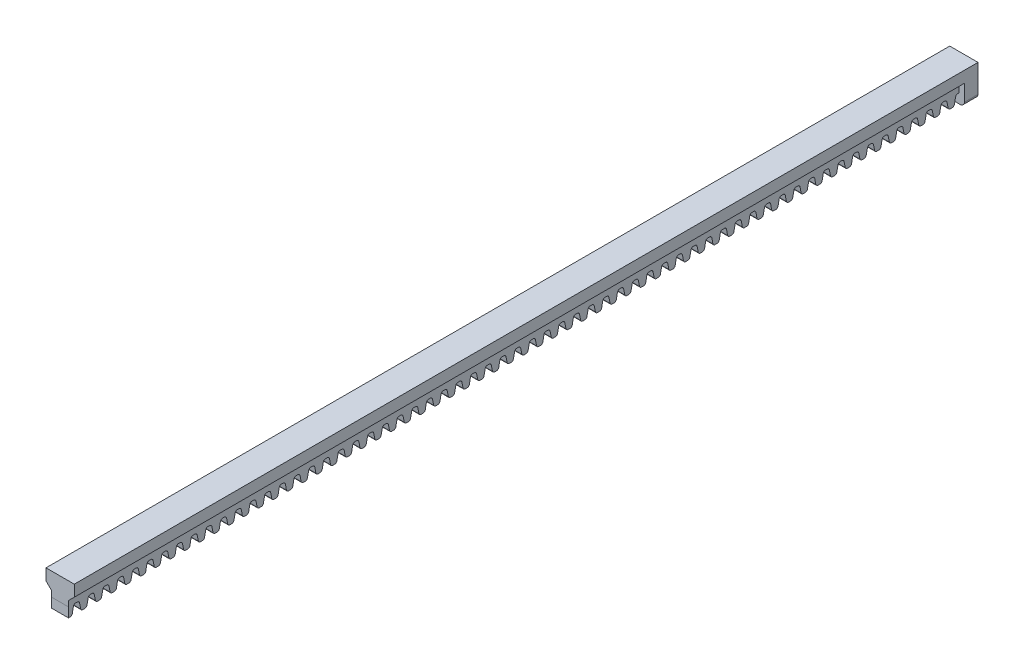
SolidWorks part; units mm, degrees
ref_plane "Ön Düzlem" through (0, 0, 0) normal (0, 0, 1) x (1, 0, 0)
ref_plane "Üst Düzlem" through (0, 0, 0) normal (0, 1, 0) x (1, 0, 0)
ref_plane "Sağ Düzlem" through (0, 0, 0) normal (1, 0, 0) x (0, 0, -1)
sketch "Sketch1" plane through (0, 0, 0) normal (0, 0, 1) x (1, 0, 0)
  line L0 (3.175, 2.54) -> (-3.175, 2.54)
  line L1 (3.175, 2.54) -> (3.175, 0)
  line L2 (-3.175, 0) -> (-1.905, -1.27)
  line L3 (-3.175, 0) -> (-3.175, 2.54)
  line L4 (1.905, -1.27) -> (3.175, 0)
  line L5 (1.905, -1.27) -> (1.905, -2.54)
  line L6 (-1.905, -1.27) -> (-1.905, -2.54)
  line L7 (-1.905, -2.54) -> (1.905, -2.54)
extrude "Boss-Extrude1" add sketch "Sketch1" along normal blind 200
sketch "Sketch2" plane through (1.905, 0, 0) normal (1, 0, 0) x (0, 0, -1)
  line L0 (-4.0649, -2.9484) -> (-4.3253, -4.2507)
  line L1 (-4.7367, -4.6515) -> (-5.2405, -4.659)
  line L2 (-5.7387, -4.2506) -> (-5.9991, -2.9484)
  line L3 (-6.4973, -2.54) -> (-3.5667, -2.54)
  line L4 (-109.7289, -2.9484) -> (-109.9893, -4.2506)
  line L5 (-6.8687, -2.54) -> (-9.7993, -2.54)
  line L6 (-7.6273, -4.2506) -> (-7.3669, -2.9484)
  line L7 (-8.6293, -4.6515) -> (-8.1255, -4.659)
  line L8 (-9.3011, -2.9484) -> (-9.0407, -4.2506)
  line L9 (-10.6689, -2.9484) -> (-10.9293, -4.2506)
  line L10 (-11.3407, -4.6515) -> (-11.8445, -4.659)
  line L11 (-12.3427, -4.2506) -> (-12.6031, -2.9484)
  line L12 (-13.1013, -2.54) -> (-10.1707, -2.54)
  line L13 (-13.4727, -2.54) -> (-16.4033, -2.54)
  line L14 (-14.2313, -4.2506) -> (-13.9709, -2.9484)
  line L15 (-15.2333, -4.6515) -> (-14.7295, -4.659)
  line L16 (-15.9051, -2.9484) -> (-15.6447, -4.2506)
  line L17 (-17.2729, -2.9484) -> (-17.5334, -4.2506)
  line L18 (-17.9447, -4.6515) -> (-18.4486, -4.659)
  line L19 (-18.9467, -4.2506) -> (-19.2072, -2.9484)
  line L20 (-19.7053, -2.54) -> (-16.7748, -2.54)
  line L21 (-20.0768, -2.54) -> (-23.0073, -2.54)
  line L22 (-20.8353, -4.2506) -> (-20.5749, -2.9484)
  line L23 (-21.8373, -4.6515) -> (-21.3335, -4.659)
  line L24 (-22.5092, -2.9484) -> (-22.2487, -4.2506)
  line L25 (-23.8769, -2.9484) -> (-24.1373, -4.2506)
  line L26 (-24.5487, -4.6515) -> (-25.0526, -4.659)
  line L27 (-25.5507, -4.2506) -> (-25.8111, -2.9484)
  line L28 (-26.3093, -2.54) -> (-23.3788, -2.54)
  line L29 (-26.6807, -2.54) -> (-29.6113, -2.54)
  line L30 (-27.4393, -4.2506) -> (-27.1789, -2.9484)
  line L31 (-28.4413, -4.6515) -> (-27.9375, -4.659)
  line L32 (-29.1131, -2.9484) -> (-28.8527, -4.2506)
  line L33 (-30.4809, -2.9484) -> (-30.7413, -4.2506)
  line L34 (-31.1527, -4.6515) -> (-31.6565, -4.659)
  line L35 (-32.1547, -4.2506) -> (-32.4151, -2.9484)
  line L36 (-32.9133, -2.54) -> (-29.9827, -2.54)
  line L37 (-33.2847, -2.54) -> (-36.2153, -2.54)
  line L38 (-34.0433, -4.2506) -> (-33.7829, -2.9484)
  line L39 (-35.0453, -4.6515) -> (-34.5415, -4.659)
  line L40 (-35.7171, -2.9484) -> (-35.4567, -4.2506)
  line L41 (-37.0849, -2.9484) -> (-37.3453, -4.2506)
  line L42 (-37.7567, -4.6515) -> (-38.2605, -4.659)
  line L43 (-38.7587, -4.2506) -> (-39.0191, -2.9484)
  line L44 (-39.5173, -2.54) -> (-36.5867, -2.54)
  line L45 (-39.8887, -2.54) -> (-42.8193, -2.54)
  line L46 (-40.6473, -4.2506) -> (-40.3869, -2.9484)
  line L47 (-41.6493, -4.6515) -> (-41.1455, -4.659)
  line L48 (-42.3211, -2.9484) -> (-42.0607, -4.2506)
  line L49 (-43.6889, -2.9484) -> (-43.9494, -4.2506)
  line L50 (-44.3607, -4.6515) -> (-44.8646, -4.659)
  line L51 (-45.3627, -4.2506) -> (-45.6231, -2.9484)
  line L52 (-46.1213, -2.54) -> (-43.1908, -2.54)
  line L53 (-46.4928, -2.54) -> (-49.4233, -2.54)
  line L54 (-47.2513, -4.2506) -> (-46.9909, -2.9484)
  line L55 (-48.2533, -4.6515) -> (-47.7495, -4.659)
  line L56 (-48.9251, -2.9484) -> (-48.6647, -4.2506)
  line L57 (-50.2929, -2.9484) -> (-50.5533, -4.2506)
  line L58 (-50.9647, -4.6515) -> (-51.4685, -4.659)
  line L59 (-51.9667, -4.2506) -> (-52.2271, -2.9484)
  line L60 (-52.7253, -2.54) -> (-49.7947, -2.54)
  line L61 (-53.0967, -2.54) -> (-56.0273, -2.54)
  line L62 (-53.8553, -4.2506) -> (-53.5949, -2.9484)
  line L63 (-54.8573, -4.6515) -> (-54.3535, -4.659)
  line L64 (-55.5291, -2.9484) -> (-55.2687, -4.2506)
  line L65 (-56.8969, -2.9484) -> (-57.1573, -4.2506)
  line L66 (-57.5687, -4.6515) -> (-58.0725, -4.659)
  line L67 (-58.5707, -4.2506) -> (-58.8311, -2.9484)
  line L68 (-59.3293, -2.54) -> (-56.3987, -2.54)
  line L69 (-59.7007, -2.54) -> (-62.6313, -2.54)
  line L70 (-60.4593, -4.2506) -> (-60.1989, -2.9484)
  line L71 (-61.4613, -4.6515) -> (-60.9575, -4.659)
  line L72 (-62.1331, -2.9484) -> (-61.8727, -4.2506)
  line L73 (-63.5009, -2.9484) -> (-63.7613, -4.2506)
  line L74 (-64.1727, -4.6515) -> (-64.6765, -4.659)
  line L75 (-65.1747, -4.2506) -> (-65.4351, -2.9484)
  line L76 (-65.9332, -2.54) -> (-63.0027, -2.54)
  line L77 (-66.3047, -2.54) -> (-69.2353, -2.54)
  line L78 (-67.0633, -4.2506) -> (-66.8029, -2.9484)
  line L79 (-68.0653, -4.6515) -> (-67.5614, -4.659)
  line L80 (-68.7371, -2.9484) -> (-68.4767, -4.2506)
  line L81 (-70.1049, -2.9484) -> (-70.3653, -4.2506)
  line L82 (-70.7767, -4.6515) -> (-71.2806, -4.659)
  line L83 (-71.7787, -4.2506) -> (-72.0391, -2.9484)
  line L84 (-72.5373, -2.54) -> (-69.6068, -2.54)
  line L85 (-72.9088, -2.54) -> (-75.8393, -2.54)
  line L86 (-73.6673, -4.2506) -> (-73.4069, -2.9484)
  line L87 (-74.6693, -4.6515) -> (-74.1655, -4.659)
  line L88 (-75.3411, -2.9484) -> (-75.0807, -4.2506)
  line L89 (-76.7089, -2.9484) -> (-76.9693, -4.2506)
  line L90 (-77.3807, -4.6515) -> (-77.8845, -4.659)
  line L91 (-78.3827, -4.2506) -> (-78.6431, -2.9484)
  line L92 (-79.1413, -2.54) -> (-76.2107, -2.54)
  line L93 (-79.5127, -2.54) -> (-82.4433, -2.54)
  line L94 (-80.2713, -4.2506) -> (-80.0109, -2.9484)
  line L95 (-81.2733, -4.6515) -> (-80.7695, -4.659)
  line L96 (-81.9451, -2.9484) -> (-81.6847, -4.2506)
  line L97 (-83.3129, -2.9484) -> (-83.5733, -4.2506)
  line L98 (-83.9847, -4.6515) -> (-84.4885, -4.659)
  line L99 (-84.9867, -4.2506) -> (-85.2471, -2.9484)
  line L100 (-85.7453, -2.54) -> (-82.8147, -2.54)
  line L101 (-86.1167, -2.54) -> (-89.0473, -2.54)
  line L102 (-86.8753, -4.2506) -> (-86.6149, -2.9484)
  line L103 (-87.8773, -4.6515) -> (-87.3735, -4.659)
  line L104 (-88.5491, -2.9484) -> (-88.2887, -4.2506)
  line L105 (-89.9169, -2.9484) -> (-90.1773, -4.2506)
  line L106 (-90.5887, -4.6515) -> (-91.0925, -4.659)
  line L107 (-91.5907, -4.2506) -> (-91.8511, -2.9484)
  line L108 (-92.3492, -2.54) -> (-89.4187, -2.54)
  line L109 (-92.7207, -2.54) -> (-95.6513, -2.54)
  line L110 (-93.4793, -4.2506) -> (-93.2189, -2.9484)
  line L111 (-94.4813, -4.6515) -> (-93.9774, -4.659)
  line L112 (-95.1531, -2.9484) -> (-94.8927, -4.2506)
  line L113 (-96.5209, -2.9484) -> (-96.7813, -4.2506)
  line L114 (-97.1927, -4.6515) -> (-97.6966, -4.659)
  line L115 (-98.1947, -4.2506) -> (-98.4551, -2.9484)
  line L116 (-98.9533, -2.54) -> (-96.0228, -2.54)
  line L117 (-99.3247, -2.54) -> (-102.2553, -2.54)
  line L118 (-100.0833, -4.2506) -> (-99.8229, -2.9484)
  line L119 (-101.0853, -4.6515) -> (-100.5815, -4.659)
  line L120 (-101.7571, -2.9484) -> (-101.4967, -4.2506)
  line L121 (-103.1249, -2.9484) -> (-103.3853, -4.2506)
  line L122 (-103.7967, -4.6515) -> (-104.3005, -4.659)
  line L123 (-104.7987, -4.2506) -> (-105.0591, -2.9484)
  line L124 (-105.5573, -2.54) -> (-102.6267, -2.54)
  line L125 (-105.9287, -2.54) -> (-108.8593, -2.54)
  line L126 (-106.6873, -4.2506) -> (-106.4269, -2.9484)
  line L127 (-107.6893, -4.6515) -> (-107.1855, -4.659)
  line L128 (-108.3611, -2.9484) -> (-108.1007, -4.2506)
  line L129 (-110.4007, -4.6515) -> (-110.9045, -4.659)
  line L130 (-111.4027, -4.2506) -> (-111.6631, -2.9484)
  line L131 (-112.1613, -2.54) -> (-109.2307, -2.54)
  line L132 (-112.5327, -2.54) -> (-115.4633, -2.54)
  line L133 (-113.2913, -4.2506) -> (-113.0309, -2.9484)
  line L134 (-114.2933, -4.6515) -> (-113.7895, -4.659)
  line L135 (-114.9651, -2.9484) -> (-114.7047, -4.2506)
  line L136 (-116.3329, -2.9484) -> (-116.5933, -4.2506)
  line L137 (-117.0047, -4.6515) -> (-117.5085, -4.659)
  line L138 (-118.0067, -4.2506) -> (-118.2671, -2.9484)
  line L139 (-118.7652, -2.54) -> (-115.8347, -2.54)
  line L140 (-119.1367, -2.54) -> (-122.0673, -2.54)
  line L141 (-119.8953, -4.2506) -> (-119.6349, -2.9484)
  line L142 (-120.8973, -4.6515) -> (-120.3934, -4.659)
  line L143 (-121.5691, -2.9484) -> (-121.3087, -4.2506)
  line L144 (-122.9369, -2.9484) -> (-123.1973, -4.2506)
  line L145 (-123.6087, -4.6515) -> (-124.1126, -4.659)
  line L146 (-124.6107, -4.2506) -> (-124.8711, -2.9484)
  line L147 (-125.3693, -2.54) -> (-122.4388, -2.54)
  line L148 (-125.7408, -2.54) -> (-128.6713, -2.54)
  line L149 (-126.4993, -4.2506) -> (-126.2389, -2.9484)
  line L150 (-127.5013, -4.6515) -> (-126.9975, -4.659)
  line L151 (-128.1731, -2.9484) -> (-127.9127, -4.2506)
  line L152 (-129.5409, -2.9484) -> (-129.8013, -4.2506)
  line L153 (-130.2127, -4.6515) -> (-130.7165, -4.659)
  line L154 (-131.2147, -4.2506) -> (-131.4751, -2.9484)
  line L155 (-131.9733, -2.54) -> (-129.0427, -2.54)
  line L157 (-198.4192, -2.54) -> (-200, -2.54)
  line L158 (-175.8034, -2.9484) -> (-176.0638, -4.2506)
  line L159 (-176.4752, -4.6515) -> (-176.979, -4.659)
  line L160 (-200, -2.54) -> (0, -2.54) construction
  line L162 (-177.4772, -4.2506) -> (-177.7376, -2.9484)
  line L163 (-0.2651, -2.54) -> (-3.1956, -2.54)
  line L164 (-1.0237, -4.2506) -> (-0.7632, -2.9484)
  line L165 (-2.0257, -4.6515) -> (-1.5218, -4.659)
  line L166 (-2.6975, -2.9484) -> (-2.437, -4.2507)
  line L167 (-178.2358, -2.54) -> (-175.3052, -2.54)
  line L168 (-178.6072, -2.54) -> (-181.5378, -2.54)
  line L169 (-179.3658, -4.2506) -> (-179.1054, -2.9484)
  line L170 (-180.3678, -4.6515) -> (-179.864, -4.659)
  line L171 (-181.0396, -2.9484) -> (-180.7792, -4.2506)
  line L172 (-182.4074, -2.9484) -> (-182.6678, -4.2506)
  line L173 (-183.0792, -4.6515) -> (-183.583, -4.659)
  line L174 (-184.0812, -4.2506) -> (-184.3416, -2.9484)
  line L175 (-184.8398, -2.54) -> (-181.9092, -2.54)
  line L176 (-185.2112, -2.54) -> (-188.1417, -2.54)
  line L177 (-185.9698, -4.2506) -> (-185.7094, -2.9484)
  line L178 (-186.9718, -4.6515) -> (-186.4679, -4.659)
  line L179 (-187.6436, -2.9484) -> (-187.3832, -4.2506)
  line L180 (-189.0113, -2.9484) -> (-189.2718, -4.2506)
  line L181 (-189.6832, -4.6515) -> (-190.187, -4.659)
  line L182 (-190.6852, -4.2506) -> (-190.9456, -2.9484)
  line L183 (-191.4437, -2.54) -> (-188.5132, -2.54)
  line L184 (-191.8152, -2.54) -> (-194.7457, -2.54)
  line L185 (-192.5738, -4.2506) -> (-192.3133, -2.9484)
  line L186 (-193.5758, -4.6515) -> (-193.0719, -4.659)
  line L187 (-194.2476, -2.9484) -> (-193.9871, -4.2506)
  line L188 (-195.6154, -2.9484) -> (-195.8758, -4.2506)
  line L189 (-196.2872, -4.6515) -> (-196.791, -4.659)
  line L190 (-197.2892, -4.2506) -> (-197.5496, -2.9484)
  line L191 (-198.0478, -2.54) -> (-195.1172, -2.54)
  line L192 (-199.1778, -4.2506) -> (-198.9174, -2.9484)
  line L194 (-152.1912, -2.54) -> (-155.1217, -2.54)
  line L195 (-152.9498, -4.2506) -> (-152.6894, -2.9484)
  line L196 (-153.9518, -4.6515) -> (-153.448, -4.659)
  line L197 (-155.9914, -2.9484) -> (-156.2518, -4.2506)
  line L198 (-156.6632, -4.6515) -> (-157.167, -4.659)
  line L199 (-157.6652, -4.2506) -> (-157.9256, -2.9484)
  line L200 (-158.4238, -2.54) -> (-155.4932, -2.54)
  line L201 (-158.7952, -2.54) -> (-161.7257, -2.54)
  line L202 (-159.5538, -4.2506) -> (-159.2934, -2.9484)
  line L203 (-160.5558, -4.6515) -> (-160.052, -4.659)
  line L204 (-161.2276, -2.9484) -> (-160.9672, -4.2506)
  line L205 (-162.5954, -2.9484) -> (-162.8558, -4.2506)
  line L206 (-163.2672, -4.6515) -> (-163.771, -4.659)
  line L207 (-164.2692, -4.2506) -> (-164.5296, -2.9484)
  line L208 (-165.0277, -2.54) -> (-162.0972, -2.54)
  line L209 (-165.3992, -2.54) -> (-168.3297, -2.54)
  line L210 (-166.1578, -4.2506) -> (-165.8973, -2.9484)
  line L211 (-167.1598, -4.6515) -> (-166.6559, -4.659)
  line L212 (-167.8316, -2.9484) -> (-167.5711, -4.2506)
  line L213 (-169.1994, -2.9484) -> (-169.4598, -4.2506)
  line L214 (-169.8712, -4.6515) -> (-170.375, -4.659)
  line L215 (-170.8732, -4.2506) -> (-171.1336, -2.9484)
  line L216 (-171.6318, -2.54) -> (-168.7012, -2.54)
  line L217 (-172.0032, -2.54) -> (-174.9338, -2.54)
  line L218 (-172.7618, -4.2506) -> (-172.5014, -2.9484)
  line L219 (-173.7638, -4.6515) -> (-173.26, -4.659)
  line L220 (-174.4356, -2.9484) -> (-174.1752, -4.2506)
  line L221 (-154.6236, -2.9484) -> (-154.3632, -4.2506)
  line L222 (-132.3792, -2.54) -> (-135.3098, -2.54)
  line L223 (-133.1378, -4.2506) -> (-132.8774, -2.9484)
  line L224 (-134.1398, -4.6515) -> (-133.6359, -4.659)
  line L225 (-134.8116, -2.9484) -> (-134.5512, -4.2506)
  line L226 (-136.1793, -2.9484) -> (-136.4398, -4.2506)
  line L227 (-136.8512, -4.6515) -> (-137.355, -4.659)
  line L228 (-137.8532, -4.2506) -> (-138.1136, -2.9484)
  line L229 (-138.6117, -2.54) -> (-135.6812, -2.54)
  line L230 (-138.9832, -2.54) -> (-141.9137, -2.54)
  line L231 (-139.7418, -4.2506) -> (-139.4813, -2.9484)
  line L232 (-140.7438, -4.6515) -> (-140.2399, -4.659)
  line L233 (-141.4156, -2.9484) -> (-141.1551, -4.2506)
  line L234 (-142.7834, -2.9484) -> (-143.0438, -4.2506)
  line L235 (-143.4552, -4.6515) -> (-143.959, -4.659)
  line L236 (-144.4572, -4.2506) -> (-144.7176, -2.9484)
  line L237 (-145.2158, -2.54) -> (-142.2852, -2.54)
  line L238 (-145.5872, -2.54) -> (-148.5178, -2.54)
  line L239 (-146.3458, -4.2506) -> (-146.0854, -2.9484)
  line L240 (-147.3478, -4.6515) -> (-146.844, -4.659)
  line L241 (-148.0196, -2.9484) -> (-147.7592, -4.2506)
  line L242 (-149.3874, -2.9484) -> (-149.6478, -4.2506)
  line L243 (-150.0592, -4.6515) -> (-150.563, -4.659)
  line L244 (-151.0612, -4.2506) -> (-151.3216, -2.9484)
  line L245 (-151.8198, -2.54) -> (-148.8892, -2.54)
  line L246 (-200, -2.54) -> (-200.0313, -4.6537)
  line L247 (-200.0313, -4.6537) -> (-199.676, -4.659)
  arc A0 (-4.0649, -2.9484) -> (-3.5667, -2.54) centre (-3.5667, -3.048) cw
  arc A1 (-4.3253, -4.2507) -> (-4.7367, -4.6515) centre (-4.8234, -4.151) cw
  arc A2 (-5.2405, -4.659) -> (-5.7387, -4.2506) centre (-5.2405, -4.151) cw
  arc A3 (-5.9991, -2.9484) -> (-6.4973, -2.54) centre (-6.4973, -3.048) ccw
  arc A4 (-7.3669, -2.9484) -> (-6.8687, -2.54) centre (-6.8687, -3.048) cw
  arc A5 (-8.1255, -4.659) -> (-7.6273, -4.2506) centre (-8.1255, -4.151) ccw
  arc A6 (-9.0407, -4.2506) -> (-8.6293, -4.6515) centre (-8.5425, -4.151) ccw
  arc A7 (-9.3011, -2.9484) -> (-9.7993, -2.54) centre (-9.7993, -3.048) ccw
  arc A8 (-10.6689, -2.9484) -> (-10.1707, -2.54) centre (-10.1707, -3.048) cw
  arc A9 (-10.9293, -4.2506) -> (-11.3407, -4.6515) centre (-11.4275, -4.151) cw
  arc A10 (-11.8445, -4.659) -> (-12.3427, -4.2506) centre (-11.8445, -4.151) cw
  arc A11 (-12.6031, -2.9484) -> (-13.1013, -2.54) centre (-13.1013, -3.048) ccw
  arc A12 (-13.9709, -2.9484) -> (-13.4727, -2.54) centre (-13.4727, -3.048) cw
  arc A13 (-14.7295, -4.659) -> (-14.2313, -4.2506) centre (-14.7294, -4.151) ccw
  arc A14 (-15.6447, -4.2506) -> (-15.2333, -4.6515) centre (-15.1465, -4.151) ccw
  arc A15 (-15.9051, -2.9484) -> (-16.4033, -2.54) centre (-16.4033, -3.048) ccw
  arc A16 (-17.2729, -2.9484) -> (-16.7748, -2.54) centre (-16.7748, -3.048) cw
  arc A17 (-17.5334, -4.2506) -> (-17.9447, -4.6515) centre (-18.0315, -4.151) cw
  arc A18 (-18.4486, -4.659) -> (-18.9467, -4.2506) centre (-18.4486, -4.151) cw
  arc A19 (-19.2072, -2.9484) -> (-19.7053, -2.54) centre (-19.7053, -3.048) ccw
  arc A20 (-20.5749, -2.9484) -> (-20.0768, -2.54) centre (-20.0768, -3.048) cw
  arc A21 (-21.3335, -4.659) -> (-20.8353, -4.2506) centre (-21.3335, -4.151) ccw
  arc A22 (-22.2487, -4.2506) -> (-21.8373, -4.6515) centre (-21.7506, -4.151) ccw
  arc A23 (-22.5092, -2.9484) -> (-23.0073, -2.54) centre (-23.0073, -3.048) ccw
  arc A24 (-23.8769, -2.9484) -> (-23.3788, -2.54) centre (-23.3787, -3.048) cw
  arc A25 (-24.1373, -4.2506) -> (-24.5487, -4.6515) centre (-24.6355, -4.151) cw
  arc A26 (-25.0526, -4.659) -> (-25.5507, -4.2506) centre (-25.0526, -4.151) cw
  arc A27 (-25.8111, -2.9484) -> (-26.3093, -2.54) centre (-26.3093, -3.048) ccw
  arc A28 (-27.1789, -2.9484) -> (-26.6807, -2.54) centre (-26.6808, -3.048) cw
  arc A29 (-27.9375, -4.659) -> (-27.4393, -4.2506) centre (-27.9375, -4.151) ccw
  arc A30 (-28.8527, -4.2506) -> (-28.4413, -4.6515) centre (-28.3546, -4.151) ccw
  arc A31 (-29.1131, -2.9484) -> (-29.6113, -2.54) centre (-29.6113, -3.048) ccw
  arc A32 (-30.4809, -2.9484) -> (-29.9827, -2.54) centre (-29.9827, -3.048) cw
  arc A33 (-30.7413, -4.2506) -> (-31.1527, -4.6515) centre (-31.2394, -4.151) cw
  arc A34 (-31.6565, -4.659) -> (-32.1547, -4.2506) centre (-31.6565, -4.151) cw
  arc A35 (-32.4151, -2.9484) -> (-32.9133, -2.54) centre (-32.9133, -3.048) ccw
  arc A36 (-33.7829, -2.9484) -> (-33.2847, -2.54) centre (-33.2847, -3.048) cw
  arc A37 (-34.5415, -4.659) -> (-34.0433, -4.2506) centre (-34.5415, -4.151) ccw
  arc A38 (-35.4567, -4.2506) -> (-35.0453, -4.6515) centre (-34.9585, -4.151) ccw
  arc A39 (-35.7171, -2.9484) -> (-36.2153, -2.54) centre (-36.2153, -3.048) ccw
  arc A40 (-37.0849, -2.9484) -> (-36.5867, -2.54) centre (-36.5867, -3.048) cw
  arc A41 (-37.3453, -4.2506) -> (-37.7567, -4.6515) centre (-37.8435, -4.151) cw
  arc A42 (-38.2605, -4.659) -> (-38.7587, -4.2506) centre (-38.2605, -4.151) cw
  arc A43 (-39.0191, -2.9484) -> (-39.5173, -2.54) centre (-39.5173, -3.048) ccw
  arc A44 (-40.3869, -2.9484) -> (-39.8887, -2.54) centre (-39.8887, -3.048) cw
  arc A45 (-41.1455, -4.659) -> (-40.6473, -4.2506) centre (-41.1454, -4.151) ccw
  arc A46 (-42.0607, -4.2506) -> (-41.6493, -4.6515) centre (-41.5625, -4.151) ccw
  arc A47 (-42.3211, -2.9484) -> (-42.8193, -2.54) centre (-42.8193, -3.048) ccw
  arc A48 (-43.6889, -2.9484) -> (-43.1908, -2.54) centre (-43.1908, -3.048) cw
  arc A49 (-43.9494, -4.2506) -> (-44.3607, -4.6515) centre (-44.4475, -4.151) cw
  arc A50 (-44.8646, -4.659) -> (-45.3627, -4.2506) centre (-44.8646, -4.151) cw
  arc A51 (-45.6231, -2.9484) -> (-46.1213, -2.54) centre (-46.1213, -3.048) ccw
  arc A52 (-46.9909, -2.9484) -> (-46.4928, -2.54) centre (-46.4928, -3.048) cw
  arc A53 (-47.7495, -4.659) -> (-47.2513, -4.2506) centre (-47.7495, -4.151) ccw
  arc A54 (-48.6647, -4.2506) -> (-48.2533, -4.6515) centre (-48.1666, -4.151) ccw
  arc A55 (-48.9251, -2.9484) -> (-49.4233, -2.54) centre (-49.4233, -3.048) ccw
  arc A56 (-50.2929, -2.9484) -> (-49.7947, -2.54) centre (-49.7947, -3.048) cw
  arc A57 (-50.5533, -4.2506) -> (-50.9647, -4.6515) centre (-51.0515, -4.151) cw
  arc A58 (-51.4685, -4.659) -> (-51.9667, -4.2506) centre (-51.4686, -4.151) cw
  arc A59 (-52.2271, -2.9484) -> (-52.7253, -2.54) centre (-52.7253, -3.048) ccw
  arc A60 (-53.5949, -2.9484) -> (-53.0967, -2.54) centre (-53.0967, -3.048) cw
  arc A61 (-54.3535, -4.659) -> (-53.8553, -4.2506) centre (-54.3535, -4.151) ccw
  arc A62 (-55.2687, -4.2506) -> (-54.8573, -4.6515) centre (-54.7706, -4.151) ccw
  arc A63 (-55.5291, -2.9484) -> (-56.0273, -2.54) centre (-56.0273, -3.048) ccw
  arc A64 (-56.8969, -2.9484) -> (-56.3987, -2.54) centre (-56.3987, -3.048) cw
  arc A65 (-57.1573, -4.2506) -> (-57.5687, -4.6515) centre (-57.6554, -4.151) cw
  arc A66 (-58.0725, -4.659) -> (-58.5707, -4.2506) centre (-58.0725, -4.151) cw
  arc A67 (-58.8311, -2.9484) -> (-59.3293, -2.54) centre (-59.3293, -3.048) ccw
  arc A68 (-60.1989, -2.9484) -> (-59.7007, -2.54) centre (-59.7007, -3.048) cw
  arc A69 (-60.9575, -4.659) -> (-60.4593, -4.2506) centre (-60.9575, -4.151) ccw
  arc A70 (-61.8727, -4.2506) -> (-61.4613, -4.6515) centre (-61.3745, -4.151) ccw
  arc A71 (-62.1331, -2.9484) -> (-62.6313, -2.54) centre (-62.6313, -3.048) ccw
  arc A72 (-63.5009, -2.9484) -> (-63.0027, -2.54) centre (-63.0027, -3.048) cw
  arc A73 (-63.7613, -4.2506) -> (-64.1727, -4.6515) centre (-64.2594, -4.151) cw
  arc A74 (-64.6765, -4.659) -> (-65.1747, -4.2506) centre (-64.6765, -4.151) cw
  arc A75 (-65.4351, -2.9484) -> (-65.9332, -2.54) centre (-65.9332, -3.048) ccw
  arc A76 (-66.8029, -2.9484) -> (-66.3047, -2.54) centre (-66.3047, -3.048) cw
  arc A77 (-67.5614, -4.659) -> (-67.0633, -4.2506) centre (-67.5614, -4.151) ccw
  arc A78 (-68.4767, -4.2506) -> (-68.0653, -4.6515) centre (-67.9785, -4.151) ccw
  arc A79 (-68.7371, -2.9484) -> (-69.2353, -2.54) centre (-69.2353, -3.048) ccw
  arc A80 (-70.1049, -2.9484) -> (-69.6068, -2.54) centre (-69.6067, -3.048) cw
  arc A81 (-70.3653, -4.2506) -> (-70.7767, -4.6515) centre (-70.8635, -4.151) cw
  arc A82 (-71.2806, -4.659) -> (-71.7787, -4.2506) centre (-71.2806, -4.151) cw
  arc A83 (-72.0391, -2.9484) -> (-72.5373, -2.54) centre (-72.5373, -3.048) ccw
  arc A84 (-73.4069, -2.9484) -> (-72.9088, -2.54) centre (-72.9088, -3.048) cw
  arc A85 (-74.1655, -4.659) -> (-73.6673, -4.2506) centre (-74.1655, -4.151) ccw
  arc A86 (-75.0807, -4.2506) -> (-74.6693, -4.6515) centre (-74.5826, -4.151) ccw
  arc A87 (-75.3411, -2.9484) -> (-75.8393, -2.54) centre (-75.8393, -3.048) ccw
  arc A88 (-76.7089, -2.9484) -> (-76.2107, -2.54) centre (-76.2107, -3.048) cw
  arc A89 (-76.9693, -4.2506) -> (-77.3807, -4.6515) centre (-77.4675, -4.151) cw
  arc A90 (-77.8845, -4.659) -> (-78.3827, -4.2506) centre (-77.8845, -4.151) cw
  arc A91 (-78.6431, -2.9484) -> (-79.1413, -2.54) centre (-79.1413, -3.048) ccw
  arc A92 (-80.0109, -2.9484) -> (-79.5127, -2.54) centre (-79.5127, -3.048) cw
  arc A93 (-80.7695, -4.659) -> (-80.2713, -4.2506) centre (-80.7695, -4.151) ccw
  arc A94 (-81.6847, -4.2506) -> (-81.2733, -4.6515) centre (-81.1866, -4.151) ccw
  arc A95 (-81.9451, -2.9484) -> (-82.4433, -2.54) centre (-82.4433, -3.048) ccw
  arc A96 (-83.3129, -2.9484) -> (-82.8147, -2.54) centre (-82.8147, -3.048) cw
  arc A97 (-83.5733, -4.2506) -> (-83.9847, -4.6515) centre (-84.0714, -4.151) cw
  arc A98 (-84.4885, -4.659) -> (-84.9867, -4.2506) centre (-84.4885, -4.151) cw
  arc A99 (-85.2471, -2.9484) -> (-85.7453, -2.54) centre (-85.7453, -3.048) ccw
  arc A100 (-86.6149, -2.9484) -> (-86.1167, -2.54) centre (-86.1167, -3.048) cw
  arc A101 (-87.3735, -4.659) -> (-86.8753, -4.2506) centre (-87.3735, -4.151) ccw
  arc A102 (-88.2887, -4.2506) -> (-87.8773, -4.6515) centre (-87.7905, -4.151) ccw
  arc A103 (-88.5491, -2.9484) -> (-89.0473, -2.54) centre (-89.0473, -3.048) ccw
  arc A104 (-89.9169, -2.9484) -> (-89.4187, -2.54) centre (-89.4187, -3.048) cw
  arc A105 (-90.1773, -4.2506) -> (-90.5887, -4.6515) centre (-90.6754, -4.151) cw
  arc A106 (-91.0925, -4.659) -> (-91.5907, -4.2506) centre (-91.0925, -4.151) cw
  arc A107 (-91.8511, -2.9484) -> (-92.3492, -2.54) centre (-92.3492, -3.048) ccw
  arc A108 (-93.2189, -2.9484) -> (-92.7207, -2.54) centre (-92.7207, -3.048) cw
  arc A109 (-93.9774, -4.659) -> (-93.4793, -4.2506) centre (-93.9774, -4.151) ccw
  arc A110 (-94.8927, -4.2506) -> (-94.4813, -4.6515) centre (-94.3945, -4.151) ccw
  arc A111 (-95.1531, -2.9484) -> (-95.6513, -2.54) centre (-95.6513, -3.048) ccw
  arc A112 (-96.5209, -2.9484) -> (-96.0228, -2.54) centre (-96.0227, -3.048) cw
  arc A113 (-96.7813, -4.2506) -> (-97.1927, -4.6515) centre (-97.2795, -4.151) cw
  arc A114 (-97.6966, -4.659) -> (-98.1947, -4.2506) centre (-97.6966, -4.151) cw
  arc A115 (-98.4551, -2.9484) -> (-98.9533, -2.54) centre (-98.9533, -3.048) ccw
  arc A116 (-99.8229, -2.9484) -> (-99.3247, -2.54) centre (-99.3248, -3.048) cw
  arc A117 (-100.5815, -4.659) -> (-100.0833, -4.2506) centre (-100.5815, -4.151) ccw
  arc A118 (-101.4967, -4.2506) -> (-101.0853, -4.6515) centre (-100.9986, -4.151) ccw
  arc A119 (-101.7571, -2.9484) -> (-102.2553, -2.54) centre (-102.2553, -3.048) ccw
  arc A120 (-103.1249, -2.9484) -> (-102.6267, -2.54) centre (-102.6267, -3.048) cw
  arc A121 (-103.3853, -4.2506) -> (-103.7967, -4.6515) centre (-103.8835, -4.151) cw
  arc A122 (-104.3005, -4.659) -> (-104.7987, -4.2506) centre (-104.3005, -4.151) cw
  arc A123 (-105.0591, -2.9484) -> (-105.5573, -2.54) centre (-105.5573, -3.048) ccw
  arc A124 (-106.4269, -2.9484) -> (-105.9287, -2.54) centre (-105.9287, -3.048) cw
  arc A125 (-107.1855, -4.659) -> (-106.6873, -4.2506) centre (-107.1855, -4.151) ccw
  arc A126 (-108.1007, -4.2506) -> (-107.6893, -4.6515) centre (-107.6026, -4.151) ccw
  arc A127 (-108.3611, -2.9484) -> (-108.8593, -2.54) centre (-108.8593, -3.048) ccw
  arc A128 (-109.7289, -2.9484) -> (-109.2307, -2.54) centre (-109.2307, -3.048) cw
  arc A129 (-109.9893, -4.2506) -> (-110.4007, -4.6515) centre (-110.4874, -4.151) cw
  arc A130 (-110.9045, -4.659) -> (-111.4027, -4.2506) centre (-110.9045, -4.151) cw
  arc A131 (-111.6631, -2.9484) -> (-112.1613, -2.54) centre (-112.1613, -3.048) ccw
  arc A132 (-113.0309, -2.9484) -> (-112.5327, -2.54) centre (-112.5327, -3.048) cw
  arc A133 (-113.7895, -4.659) -> (-113.2913, -4.2506) centre (-113.7895, -4.151) ccw
  arc A134 (-114.7047, -4.2506) -> (-114.2933, -4.6515) centre (-114.2065, -4.151) ccw
  arc A135 (-114.9651, -2.9484) -> (-115.4633, -2.54) centre (-115.4633, -3.048) ccw
  arc A136 (-116.3329, -2.9484) -> (-115.8347, -2.54) centre (-115.8347, -3.048) cw
  arc A137 (-116.5933, -4.2506) -> (-117.0047, -4.6515) centre (-117.0914, -4.151) cw
  arc A138 (-117.5085, -4.659) -> (-118.0067, -4.2506) centre (-117.5085, -4.151) cw
  arc A139 (-118.2671, -2.9484) -> (-118.7652, -2.54) centre (-118.7652, -3.048) ccw
  arc A140 (-119.6349, -2.9484) -> (-119.1367, -2.54) centre (-119.1367, -3.048) cw
  arc A141 (-120.3934, -4.659) -> (-119.8953, -4.2506) centre (-120.3934, -4.151) ccw
  arc A142 (-121.3087, -4.2506) -> (-120.8973, -4.6515) centre (-120.8105, -4.151) ccw
  arc A143 (-121.5691, -2.9484) -> (-122.0673, -2.54) centre (-122.0673, -3.048) ccw
  arc A144 (-122.9369, -2.9484) -> (-122.4388, -2.54) centre (-122.4387, -3.048) cw
  arc A145 (-123.1973, -4.2506) -> (-123.6087, -4.6515) centre (-123.6955, -4.151) cw
  arc A146 (-124.1126, -4.659) -> (-124.6107, -4.2506) centre (-124.1126, -4.151) cw
  arc A147 (-124.8711, -2.9484) -> (-125.3693, -2.54) centre (-125.3693, -3.048) ccw
  arc A148 (-126.2389, -2.9484) -> (-125.7408, -2.54) centre (-125.7408, -3.048) cw
  arc A149 (-126.9975, -4.659) -> (-126.4993, -4.2506) centre (-126.9975, -4.151) ccw
  arc A150 (-127.9127, -4.2506) -> (-127.5013, -4.6515) centre (-127.4146, -4.151) ccw
  arc A151 (-128.1731, -2.9484) -> (-128.6713, -2.54) centre (-128.6713, -3.048) ccw
  arc A152 (-129.5409, -2.9484) -> (-129.0427, -2.54) centre (-129.0427, -3.048) cw
  arc A153 (-129.8013, -4.2506) -> (-130.2127, -4.6515) centre (-130.2995, -4.151) cw
  arc A154 (-130.7165, -4.659) -> (-131.2147, -4.2506) centre (-130.7165, -4.151) cw
  arc A155 (-131.4751, -2.9484) -> (-131.9733, -2.54) centre (-131.9733, -3.048) ccw
  arc A157 (-0.7632, -2.9484) -> (-0.2651, -2.54) centre (-0.2651, -3.048) cw
  arc A158 (-1.5218, -4.659) -> (-1.0237, -4.2506) centre (-1.5218, -4.151) ccw
  arc A159 (-2.437, -4.2507) -> (-2.0257, -4.6515) centre (-1.9389, -4.151) ccw
  arc A160 (-2.6975, -2.9484) -> (-3.1956, -2.54) centre (-3.1956, -3.048) ccw
  arc A161 (-175.8034, -2.9484) -> (-175.3052, -2.54) centre (-175.3052, -3.048) cw
  arc A162 (-176.0638, -4.2506) -> (-176.4752, -4.6515) centre (-176.562, -4.151) cw
  arc A163 (-176.979, -4.659) -> (-177.4772, -4.2506) centre (-176.979, -4.151) cw
  arc A164 (-177.7376, -2.9484) -> (-178.2358, -2.54) centre (-178.2358, -3.048) ccw
  arc A165 (-179.1054, -2.9484) -> (-178.6072, -2.54) centre (-178.6072, -3.048) cw
  arc A166 (-179.864, -4.659) -> (-179.3658, -4.2506) centre (-179.864, -4.151) ccw
  arc A167 (-180.7792, -4.2506) -> (-180.3678, -4.6515) centre (-180.2811, -4.151) ccw
  arc A168 (-181.0396, -2.9484) -> (-181.5378, -2.54) centre (-181.5378, -3.048) ccw
  arc A169 (-182.4074, -2.9484) -> (-181.9092, -2.54) centre (-181.9092, -3.048) cw
  arc A170 (-182.6678, -4.2506) -> (-183.0792, -4.6515) centre (-183.1659, -4.151) cw
  arc A171 (-183.583, -4.659) -> (-184.0812, -4.2506) centre (-183.583, -4.151) cw
  arc A172 (-184.3416, -2.9484) -> (-184.8398, -2.54) centre (-184.8397, -3.048) ccw
  arc A173 (-185.7094, -2.9484) -> (-185.2112, -2.54) centre (-185.2112, -3.048) cw
  arc A174 (-186.4679, -4.659) -> (-185.9698, -4.2506) centre (-186.4679, -4.151) ccw
  arc A175 (-187.3832, -4.2506) -> (-186.9718, -4.6515) centre (-186.885, -4.151) ccw
  arc A176 (-187.6436, -2.9484) -> (-188.1417, -2.54) centre (-188.1418, -3.048) ccw
  arc A177 (-189.0113, -2.9484) -> (-188.5132, -2.54) centre (-188.5132, -3.048) cw
  arc A178 (-189.2718, -4.2506) -> (-189.6832, -4.6515) centre (-189.7699, -4.151) cw
  arc A179 (-190.187, -4.659) -> (-190.6852, -4.2506) centre (-190.187, -4.151) cw
  arc A180 (-190.9456, -2.9484) -> (-191.4437, -2.54) centre (-191.4437, -3.048) ccw
  arc A181 (-192.3133, -2.9484) -> (-191.8152, -2.54) centre (-191.8152, -3.048) cw
  arc A182 (-193.0719, -4.659) -> (-192.5738, -4.2506) centre (-193.0719, -4.151) ccw
  arc A183 (-193.9871, -4.2506) -> (-193.5758, -4.6515) centre (-193.489, -4.151) ccw
  arc A184 (-194.2476, -2.9484) -> (-194.7457, -2.54) centre (-194.7457, -3.048) ccw
  arc A185 (-195.6154, -2.9484) -> (-195.1172, -2.54) centre (-195.1172, -3.048) cw
  arc A186 (-195.8758, -4.2506) -> (-196.2872, -4.6515) centre (-196.374, -4.151) cw
  arc A187 (-196.791, -4.659) -> (-197.2892, -4.2506) centre (-196.791, -4.151) cw
  arc A188 (-197.5496, -2.9484) -> (-198.0478, -2.54) centre (-198.0478, -3.048) ccw
  arc A189 (-198.9174, -2.9484) -> (-198.4192, -2.54) centre (-198.4192, -3.048) cw
  arc A190 (-199.676, -4.659) -> (-199.1778, -4.2506) centre (-199.676, -4.151) ccw
  arc A191 (-152.6894, -2.9484) -> (-152.1912, -2.54) centre (-152.1912, -3.048) cw
  arc A192 (-153.448, -4.659) -> (-152.9498, -4.2506) centre (-153.448, -4.151) ccw
  arc A193 (-154.3632, -4.2506) -> (-153.9518, -4.6515) centre (-153.8651, -4.151) ccw
  arc A194 (-154.6236, -2.9484) -> (-155.1217, -2.54) centre (-155.1218, -3.048) ccw
  arc A195 (-155.9914, -2.9484) -> (-155.4932, -2.54) centre (-155.4932, -3.048) cw
  arc A196 (-156.2518, -4.2506) -> (-156.6632, -4.6515) centre (-156.7499, -4.151) cw
  arc A197 (-157.167, -4.659) -> (-157.6652, -4.2506) centre (-157.167, -4.151) cw
  arc A198 (-157.9256, -2.9484) -> (-158.4238, -2.54) centre (-158.4238, -3.048) ccw
  arc A199 (-159.2934, -2.9484) -> (-158.7952, -2.54) centre (-158.7952, -3.048) cw
  arc A200 (-160.052, -4.659) -> (-159.5538, -4.2506) centre (-160.0519, -4.151) ccw
  arc A201 (-160.9672, -4.2506) -> (-160.5558, -4.6515) centre (-160.469, -4.151) ccw
  arc A202 (-161.2276, -2.9484) -> (-161.7257, -2.54) centre (-161.7258, -3.048) ccw
  arc A203 (-162.5954, -2.9484) -> (-162.0972, -2.54) centre (-162.0972, -3.048) cw
  arc A204 (-162.8558, -4.2506) -> (-163.2672, -4.6515) centre (-163.3539, -4.151) cw
  arc A205 (-163.771, -4.659) -> (-164.2692, -4.2506) centre (-163.771, -4.151) cw
  arc A206 (-164.5296, -2.9484) -> (-165.0277, -2.54) centre (-165.0277, -3.048) ccw
  arc A207 (-165.8973, -2.9484) -> (-165.3992, -2.54) centre (-165.3992, -3.048) cw
  arc A208 (-166.6559, -4.659) -> (-166.1578, -4.2506) centre (-166.6559, -4.151) ccw
  arc A209 (-167.5711, -4.2506) -> (-167.1598, -4.6515) centre (-167.073, -4.151) ccw
  arc A210 (-167.8316, -2.9484) -> (-168.3297, -2.54) centre (-168.3297, -3.048) ccw
  arc A211 (-169.1994, -2.9484) -> (-168.7012, -2.54) centre (-168.7012, -3.048) cw
  arc A212 (-169.4598, -4.2506) -> (-169.8712, -4.6515) centre (-169.958, -4.151) cw
  arc A213 (-170.375, -4.659) -> (-170.8732, -4.2506) centre (-170.3751, -4.151) cw
  arc A214 (-171.1336, -2.9484) -> (-171.6318, -2.54) centre (-171.6318, -3.048) ccw
  arc A215 (-172.5014, -2.9484) -> (-172.0032, -2.54) centre (-172.0032, -3.048) cw
  arc A216 (-173.26, -4.659) -> (-172.7618, -4.2506) centre (-173.26, -4.151) ccw
  arc A217 (-174.1752, -4.2506) -> (-173.7638, -4.6515) centre (-173.677, -4.151) ccw
  arc A218 (-174.4356, -2.9484) -> (-174.9338, -2.54) centre (-174.9338, -3.048) ccw
  arc A219 (-132.8774, -2.9484) -> (-132.3792, -2.54) centre (-132.3792, -3.048) cw
  arc A220 (-133.6359, -4.659) -> (-133.1378, -4.2506) centre (-133.6359, -4.151) ccw
  arc A221 (-134.5512, -4.2506) -> (-134.1398, -4.6515) centre (-134.053, -4.151) ccw
  arc A222 (-134.8116, -2.9484) -> (-135.3098, -2.54) centre (-135.3098, -3.048) ccw
  arc A223 (-136.1793, -2.9484) -> (-135.6812, -2.54) centre (-135.6812, -3.048) cw
  arc A224 (-136.4398, -4.2506) -> (-136.8512, -4.6515) centre (-136.9379, -4.151) cw
  arc A225 (-137.355, -4.659) -> (-137.8532, -4.2506) centre (-137.355, -4.151) cw
  arc A226 (-138.1136, -2.9484) -> (-138.6117, -2.54) centre (-138.6117, -3.048) ccw
  arc A227 (-139.4813, -2.9484) -> (-138.9832, -2.54) centre (-138.9832, -3.048) cw
  arc A228 (-140.2399, -4.659) -> (-139.7418, -4.2506) centre (-140.2399, -4.151) ccw
  arc A229 (-141.1551, -4.2506) -> (-140.7438, -4.6515) centre (-140.657, -4.151) ccw
  arc A230 (-141.4156, -2.9484) -> (-141.9137, -2.54) centre (-141.9137, -3.048) ccw
  arc A231 (-142.7834, -2.9484) -> (-142.2852, -2.54) centre (-142.2852, -3.048) cw
  arc A232 (-143.0438, -4.2506) -> (-143.4552, -4.6515) centre (-143.542, -4.151) cw
  arc A233 (-143.959, -4.659) -> (-144.4572, -4.2506) centre (-143.959, -4.151) cw
  arc A234 (-144.7176, -2.9484) -> (-145.2158, -2.54) centre (-145.2158, -3.048) ccw
  arc A235 (-146.0854, -2.9484) -> (-145.5872, -2.54) centre (-145.5872, -3.048) cw
  arc A236 (-146.844, -4.659) -> (-146.3458, -4.2506) centre (-146.844, -4.151) ccw
  arc A237 (-147.7592, -4.2506) -> (-147.3478, -4.6515) centre (-147.261, -4.151) ccw
  arc A238 (-148.0196, -2.9484) -> (-148.5178, -2.54) centre (-148.5178, -3.048) ccw
  arc A239 (-149.3874, -2.9484) -> (-148.8892, -2.54) centre (-148.8892, -3.048) cw
  arc A240 (-149.6478, -4.2506) -> (-150.0592, -4.6515) centre (-150.146, -4.151) cw
  arc A241 (-150.563, -4.659) -> (-151.0612, -4.2506) centre (-150.563, -4.151) cw
  arc A242 (-151.3216, -2.9484) -> (-151.8198, -2.54) centre (-151.8198, -3.048) ccw
  point P468 (0, 0)
extrude "Boss-Extrude2" add sketch "Sketch2" against normal up to surface (3.81 mm away) up to face at (-1.905, -1.905, 100)
sketch "Sketch3" plane through (0, 0, 0) normal (0, 0, -1) x (-1, 0, 0)
  line L0 (-3.175, 2.54) -> (-3.175, -3.6837)
  line L1 (3.175, 2.54) -> (3.175, -3.6837)
  line L2 (-3.175, 2.54) -> (3.175, 2.54)
  line L7 (1.905, -4.659) -> (1.905, -4.6515)
  line L8 (-1.905, -4.659) -> (1.905, -4.659)
  line L9 (-1.905, -4.6515) -> (-1.905, -4.659)
  line L10 (1.905, -4.6515) -> (-1.905, -4.6515)
  line L11 (1.905, -4.659) -> (1.905, -4.6515)
  line L13 (-1.905, -4.6515) -> (-1.905, -4.659)
  line L14 (1.905, -4.6515) -> (-1.905, -4.6515)
  arc A0 (-3.175, -3.6837) -> (-1.905, -4.659) centre (-2.0523, -3.5363) ccw
  arc A1 (3.175, -3.6837) -> (1.905, -4.659) centre (2.0523, -3.5363) cw
  dimension "D1" = 0
extrude "Boss-Extrude4" add sketch "Sketch3" along normal blind 3
